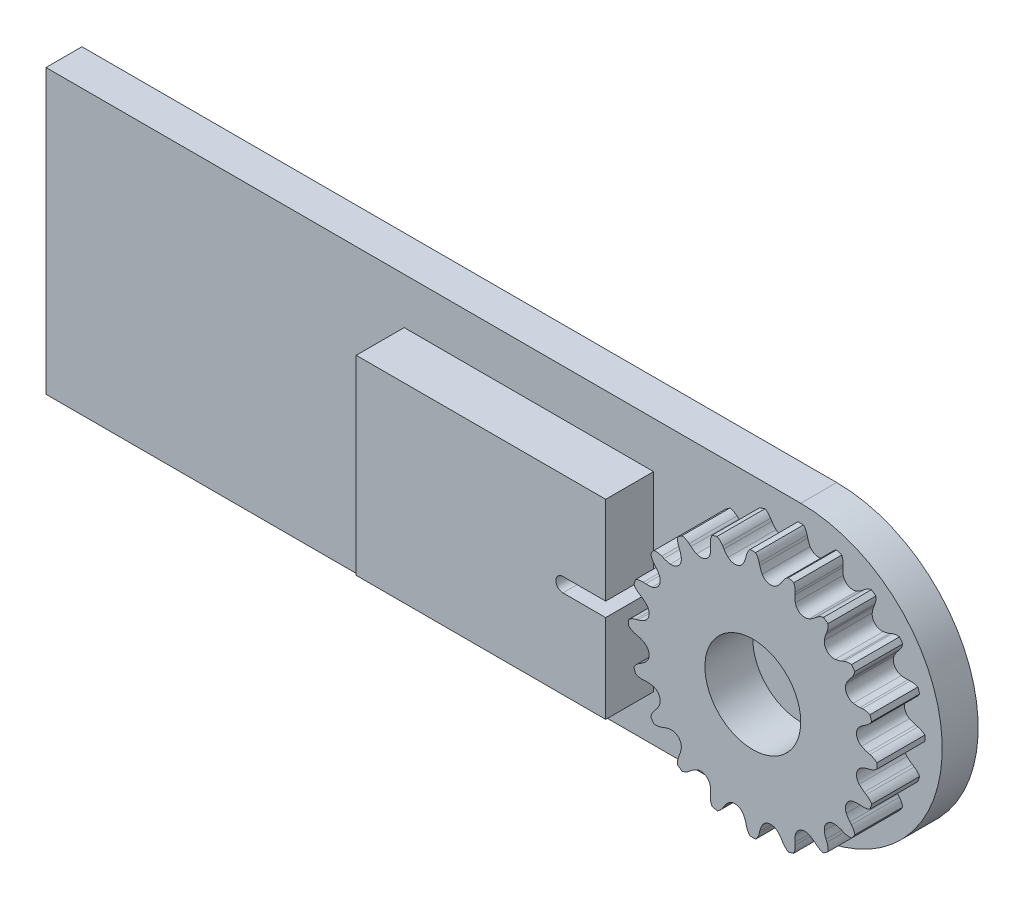
SolidWorks part; units mm, degrees
ref_plane "Front Plane" through (0, 0, 0) normal (0, 0, 1) x (1, 0, 0)
ref_plane "Top Plane" through (0, 0, 0) normal (0, 1, 0) x (1, 0, 0)
ref_plane "Right Plane" through (0, 0, 0) normal (1, 0, 0) x (0, 0, -1)
sketch "Sketch3" plane through (0, 0, 0) normal (1, 0, 0) x (0, 0, -1)
  line L5 (6.35, -43.7634) -> (-6.35, -43.7634)
  line L6 (6.35, -43.7634) -> (6.35, 43.7634)
  line L7 (6.35, 43.7634) -> (-6.35, 43.7634)
  line L8 (-6.35, -43.7634) -> (-6.35, 43.7634)
  line L9 (6.35, -43.7634) -> (-6.35, 43.7634) construction
  line L10 (6.35, 43.7634) -> (-6.35, -43.7634) construction
  line L11 (6.35, -37.5) -> (15.875, -37.5)
  line L12 (6.35, -37.5) -> (6.35, 37.5)
  line L13 (6.35, 37.5) -> (15.875, 37.5)
  line L14 (15.875, -37.5) -> (15.875, 37.5)
  line L15 (6.35, -37.5) -> (15.875, 37.5) construction
  line L16 (6.35, 37.5) -> (15.875, -37.5) construction
  point P0 (11.1125, 0)
  point P1 (0, 0)
  point P4 (0, 0)
  dimension "D1" = 9.525
  dimension "D2" = 12.7
  dimension "D3" = 75
extrude "Boss-Extrude3" add sketch "Sketch3" against normal blind 200 separate body contours L11 L14 L13 L6 region at (0, 0, -11.1125)
sketch "Sketch4" plane through (0, 0, -15.875) normal (0, 0, -1) x (-1, 0, 0)
  line L0 (200, 37.5) -> (0, 37.5) construction
  arc A0 (0, 37.5) -> (0, -37.5) centre (0, 0) ccw
  line M1 (0, 37.5) -> (0, -37.5)
extrude "Boss-Extrude4" add sketch "Sketch4" against normal up to surface (9.525 mm away) contours A0 M1 region at (15.9155, 0, -15.875) up to face at (-100, 0, -6.35)
sketch "Sketch1" plane through (0, 0, 0) normal (0, 0, 1) x (1, 0, 0)
  circle A0 centre (0, 0) radius 12.7
  circle A1 centre (0, 0) radius 9.525
  circle A2 centre (0, 0) radius 25
  circle A3 centre (0, 0) radius 30.319 construction
  dimension "D1" = 25.4
  dimension "D2" = 19.05
  dimension "D3" = 50
  dimension "D4" = 60.638
extrude "Boss-Extrude1" add sketch "Sketch1" against normal mid plane 12.7 separate body contours A2 A0 region at (-24.2929, 0, 0)
sketch "Sketch2" plane through (0, 0, 6.35) normal (0, 0, -1) x (-1, 0, 0)
  line L0 (-24.1305, -19.6378) -> (-23.5464, -19.3994)
  line L1 (-19.3994, -23.5464) -> (-19.6378, -24.1305)
  line L2 (-16.8811, -26.1334) -> (-16.3992, -25.7262)
  line L3 (-11.1737, -28.3887) -> (-11.2199, -29.0179)
  line L4 (-7.9792, -30.0709) -> (-7.6467, -29.5347)
  line L5 (-1.8543, -30.4521) -> (-1.7038, -31.0648)
  line L6 (1.7038, -31.0648) -> (1.8543, -30.4521)
  line L7 (7.6467, -29.5347) -> (7.9792, -30.0709)
  line L8 (11.2199, -29.0179) -> (11.1737, -28.3887)
  line L9 (16.3992, -25.7262) -> (16.8811, -26.1334)
  line L10 (19.6378, -24.1305) -> (19.3994, -23.5464)
  line L11 (23.5464, -19.3994) -> (24.1305, -19.6378)
  line L12 (26.1334, -16.8811) -> (25.7262, -16.3992)
  line L13 (28.3887, -11.1737) -> (29.0179, -11.2199)
  line L14 (30.0709, -7.9792) -> (29.5347, -7.6467)
  line L15 (30.4521, -1.8543) -> (31.0648, -1.7038)
  line L16 (31.0648, 1.7038) -> (30.4521, 1.8543)
  line L17 (29.5347, 7.6467) -> (30.0709, 7.9792)
  line L18 (29.0179, 11.2199) -> (28.3887, 11.1737)
  line L19 (25.7262, 16.3992) -> (26.1334, 16.8811)
  line L20 (24.1305, 19.6378) -> (23.5464, 19.3994)
  line L21 (19.3994, 23.5464) -> (19.6378, 24.1305)
  line L22 (16.8811, 26.1334) -> (16.3992, 25.7262)
  line L23 (11.1737, 28.3887) -> (11.2199, 29.0179)
  line L24 (7.9792, 30.0709) -> (7.6467, 29.5347)
  line L25 (1.8543, 30.4521) -> (1.7038, 31.0648)
  line L26 (-1.7038, 31.0648) -> (-1.8543, 30.4521)
  line L27 (-7.6467, 29.5347) -> (-7.9792, 30.0709)
  line L28 (-11.2199, 29.0179) -> (-11.1737, 28.3887)
  line L29 (-16.3992, 25.7262) -> (-16.8811, 26.1334)
  line L30 (-19.6378, 24.1305) -> (-19.3994, 23.5464)
  line L31 (-23.5464, 19.3994) -> (-24.1305, 19.6378)
  line L32 (-26.1334, 16.8811) -> (-25.7262, 16.3992)
  line L33 (-28.3887, 11.1737) -> (-29.0179, 11.2199)
  line L34 (-30.0709, 7.9792) -> (-29.5347, 7.6467)
  line L35 (-30.4521, 1.8543) -> (-31.0648, 1.7038)
  line L36 (-31.0648, -1.7038) -> (-30.4521, -1.8543)
  line L37 (-29.5347, -7.6467) -> (-30.0709, -7.9792)
  line L38 (-29.0179, -11.2199) -> (-28.3887, -11.1737)
  line L39 (-25.7262, -16.3992) -> (-26.1334, -16.8811)
  arc A0 (-27.0344, -18.7375) -> (-26.1745, -19.921) centre (0, 0) ccw
  arc A1 (-26.1745, -19.921) -> (-24.1305, -19.6378) centre (-25.7075, -15.7735) ccw
  arc A2 (-21.8429, -18.9557) -> (-23.5464, -19.3994) centre (-21.0319, -25.5609) ccw
  arc A3 (-18.9557, -21.8429) -> (-21.8429, -18.9557) centre (-21.5272, -21.5272) ccw
  arc A4 (-19.3994, -23.5464) -> (-18.9557, -21.8429) centre (-25.5609, -21.0319) ccw
  arc A5 (-19.6378, -24.1305) -> (-19.921, -26.1745) centre (-15.7735, -25.7075) ccw
  arc A6 (-19.921, -26.1745) -> (-18.7375, -27.0344) centre (0, 0) ccw
  arc A7 (-18.7375, -27.0344) -> (-16.8811, -26.1334) centre (-19.575, -22.9455) ccw
  arc A8 (-14.9162, -24.7778) -> (-16.3992, -25.7262) centre (-12.1038, -30.8091) ccw
  arc A9 (-11.2781, -26.6315) -> (-14.9162, -24.7778) centre (-13.8213, -27.1259) ccw
  arc A10 (-11.1737, -28.3887) -> (-11.2781, -26.6315) centre (-17.8106, -27.9013) ccw
  arc A11 (-11.2199, -29.0179) -> (-10.8576, -31.0493) centre (-7.0574, -29.3236) ccw
  arc A12 (-10.8576, -31.0493) -> (-9.4663, -31.5014) centre (0, 0) ccw
  arc A13 (-9.4663, -31.5014) -> (-7.9792, -30.0709) centre (-11.5264, -27.8715) ccw
  arc A14 (-6.5294, -28.1745) -> (-7.6467, -29.5347) centre (-1.9909, -33.0415) ccw
  arc A15 (-2.4965, -28.8132) -> (-6.5294, -28.1745) centre (-4.7625, -30.0692) ccw
  arc A16 (-1.8543, -30.4521) -> (-2.4965, -28.8132) centre (-8.317, -32.0395) ccw
  arc A17 (-1.7038, -31.0648) -> (-0.7315, -32.8849) centre (2.3495, -30.0692) ccw
  arc A18 (-0.7315, -32.8849) -> (0.7315, -32.8849) centre (0, 0) ccw
  arc A19 (0.7315, -32.8849) -> (1.7038, -31.0648) centre (-2.3495, -30.0692) ccw
  arc A20 (2.4965, -28.8132) -> (1.8543, -30.4521) centre (8.317, -32.0395) ccw
  arc A21 (6.5294, -28.1745) -> (2.4965, -28.8132) centre (4.7625, -30.0692) ccw
  arc A22 (7.6467, -29.5347) -> (6.5294, -28.1745) centre (1.9909, -33.0415) ccw
  arc A23 (7.9792, -30.0709) -> (9.4663, -31.5014) centre (11.5264, -27.8715) ccw
  arc A24 (9.4663, -31.5014) -> (10.8576, -31.0493) centre (0, 0) ccw
  arc A25 (10.8576, -31.0493) -> (11.2199, -29.0179) centre (7.0574, -29.3236) ccw
  arc A26 (11.2781, -26.6315) -> (11.1737, -28.3887) centre (17.8106, -27.9013) ccw
  arc A27 (14.9162, -24.7778) -> (11.2781, -26.6315) centre (13.8213, -27.1259) ccw
  arc A28 (16.3992, -25.7262) -> (14.9162, -24.7778) centre (12.1038, -30.8091) ccw
  arc A29 (16.8811, -26.1334) -> (18.7375, -27.0344) centre (19.575, -22.9455) ccw
  arc A30 (18.7375, -27.0344) -> (19.921, -26.1745) centre (0, 0) ccw
  arc A31 (19.921, -26.1745) -> (19.6378, -24.1305) centre (15.7735, -25.7075) ccw
  arc A32 (18.9557, -21.8429) -> (19.3994, -23.5464) centre (25.5609, -21.0319) ccw
  arc A33 (21.8429, -18.9557) -> (18.9557, -21.8429) centre (21.5272, -21.5272) ccw
  arc A34 (23.5464, -19.3994) -> (21.8429, -18.9557) centre (21.0319, -25.5609) ccw
  arc A35 (24.1305, -19.6378) -> (26.1745, -19.921) centre (25.7075, -15.7735) ccw
  arc A36 (26.1745, -19.921) -> (27.0344, -18.7375) centre (0, 0) ccw
  arc A37 (27.0344, -18.7375) -> (26.1334, -16.8811) centre (22.9455, -19.575) ccw
  arc A38 (24.7778, -14.9162) -> (25.7262, -16.3992) centre (30.8091, -12.1038) ccw
  arc A39 (26.6315, -11.2781) -> (24.7778, -14.9162) centre (27.1259, -13.8213) ccw
  arc A40 (28.3887, -11.1737) -> (26.6315, -11.2781) centre (27.9013, -17.8106) ccw
  arc A41 (29.0179, -11.2199) -> (31.0493, -10.8576) centre (29.3236, -7.0574) ccw
  arc A42 (31.0493, -10.8576) -> (31.5014, -9.4663) centre (0, 0) ccw
  arc A43 (31.5014, -9.4663) -> (30.0709, -7.9792) centre (27.8715, -11.5264) ccw
  arc A44 (28.1745, -6.5294) -> (29.5347, -7.6467) centre (33.0415, -1.9909) ccw
  arc A45 (28.8132, -2.4965) -> (28.1745, -6.5294) centre (30.0692, -4.7625) ccw
  arc A46 (30.4521, -1.8543) -> (28.8132, -2.4965) centre (32.0395, -8.317) ccw
  arc A47 (31.0648, -1.7038) -> (32.8849, -0.7315) centre (30.0692, 2.3495) ccw
  arc A48 (32.8849, -0.7315) -> (32.8849, 0.7315) centre (0, 0) ccw
  arc A49 (32.8849, 0.7315) -> (31.0648, 1.7038) centre (30.0692, -2.3495) ccw
  arc A50 (28.8132, 2.4965) -> (30.4521, 1.8543) centre (32.0395, 8.317) ccw
  arc A51 (28.1745, 6.5294) -> (28.8132, 2.4965) centre (30.0692, 4.7625) ccw
  arc A52 (29.5347, 7.6467) -> (28.1745, 6.5294) centre (33.0415, 1.9909) ccw
  arc A53 (30.0709, 7.9792) -> (31.5014, 9.4663) centre (27.8715, 11.5264) ccw
  arc A54 (31.5014, 9.4663) -> (31.0493, 10.8576) centre (0, 0) ccw
  arc A55 (31.0493, 10.8576) -> (29.0179, 11.2199) centre (29.3236, 7.0574) ccw
  arc A56 (26.6315, 11.2781) -> (28.3887, 11.1737) centre (27.9013, 17.8106) ccw
  arc A57 (24.7778, 14.9162) -> (26.6315, 11.2781) centre (27.1259, 13.8213) ccw
  arc A58 (25.7262, 16.3992) -> (24.7778, 14.9162) centre (30.8091, 12.1038) ccw
  arc A59 (26.1334, 16.8811) -> (27.0344, 18.7375) centre (22.9455, 19.575) ccw
  arc A60 (27.0344, 18.7375) -> (26.1745, 19.921) centre (0, 0) ccw
  arc A61 (26.1745, 19.921) -> (24.1305, 19.6378) centre (25.7075, 15.7735) ccw
  arc A62 (21.8429, 18.9557) -> (23.5464, 19.3994) centre (21.0319, 25.5609) ccw
  arc A63 (18.9557, 21.8429) -> (21.8429, 18.9557) centre (21.5272, 21.5272) ccw
  arc A64 (19.3994, 23.5464) -> (18.9557, 21.8429) centre (25.5609, 21.0319) ccw
  arc A65 (19.6378, 24.1305) -> (19.921, 26.1745) centre (15.7735, 25.7075) ccw
  arc A66 (19.921, 26.1745) -> (18.7375, 27.0344) centre (0, 0) ccw
  arc A67 (18.7375, 27.0344) -> (16.8811, 26.1334) centre (19.575, 22.9455) ccw
  arc A68 (14.9162, 24.7778) -> (16.3992, 25.7262) centre (12.1038, 30.8091) ccw
  arc A69 (11.2781, 26.6315) -> (14.9162, 24.7778) centre (13.8213, 27.1259) ccw
  arc A70 (11.1737, 28.3887) -> (11.2781, 26.6315) centre (17.8106, 27.9013) ccw
  arc A71 (11.2199, 29.0179) -> (10.8576, 31.0493) centre (7.0574, 29.3236) ccw
  arc A72 (10.8576, 31.0493) -> (9.4663, 31.5014) centre (0, 0) ccw
  arc A73 (9.4663, 31.5014) -> (7.9792, 30.0709) centre (11.5264, 27.8715) ccw
  arc A74 (6.5294, 28.1745) -> (7.6467, 29.5347) centre (1.9909, 33.0415) ccw
  arc A75 (2.4965, 28.8132) -> (6.5294, 28.1745) centre (4.7625, 30.0692) ccw
  arc A76 (1.8543, 30.4521) -> (2.4965, 28.8132) centre (8.317, 32.0395) ccw
  arc A77 (1.7038, 31.0648) -> (0.7315, 32.8849) centre (-2.3495, 30.0692) ccw
  arc A78 (0.7315, 32.8849) -> (-0.7315, 32.8849) centre (0, 0) ccw
  arc A79 (-0.7315, 32.8849) -> (-1.7038, 31.0648) centre (2.3495, 30.0692) ccw
  arc A80 (-2.4965, 28.8132) -> (-1.8543, 30.4521) centre (-8.317, 32.0395) ccw
  arc A81 (-6.5294, 28.1745) -> (-2.4965, 28.8132) centre (-4.7625, 30.0692) ccw
  arc A82 (-7.6467, 29.5347) -> (-6.5294, 28.1745) centre (-1.9909, 33.0415) ccw
  arc A83 (-7.9792, 30.0709) -> (-9.4663, 31.5014) centre (-11.5264, 27.8715) ccw
  arc A84 (-9.4663, 31.5014) -> (-10.8576, 31.0493) centre (0, 0) ccw
  arc A85 (-10.8576, 31.0493) -> (-11.2199, 29.0179) centre (-7.0574, 29.3236) ccw
  arc A86 (-11.2781, 26.6315) -> (-11.1737, 28.3887) centre (-17.8106, 27.9013) ccw
  arc A87 (-14.9162, 24.7778) -> (-11.2781, 26.6315) centre (-13.8213, 27.1259) ccw
  arc A88 (-16.3992, 25.7262) -> (-14.9162, 24.7778) centre (-12.1038, 30.8091) ccw
  arc A89 (-16.8811, 26.1334) -> (-18.7375, 27.0344) centre (-19.575, 22.9455) ccw
  arc A90 (-18.7375, 27.0344) -> (-19.921, 26.1745) centre (0, 0) ccw
  arc A91 (-19.921, 26.1745) -> (-19.6378, 24.1305) centre (-15.7735, 25.7075) ccw
  arc A92 (-18.9557, 21.8429) -> (-19.3994, 23.5464) centre (-25.5609, 21.0319) ccw
  arc A93 (-21.8429, 18.9557) -> (-18.9557, 21.8429) centre (-21.5272, 21.5272) ccw
  arc A94 (-23.5464, 19.3994) -> (-21.8429, 18.9557) centre (-21.0319, 25.5609) ccw
  arc A95 (-24.1305, 19.6378) -> (-26.1745, 19.921) centre (-25.7075, 15.7735) ccw
  arc A96 (-26.1745, 19.921) -> (-27.0344, 18.7375) centre (0, 0) ccw
  arc A97 (-27.0344, 18.7375) -> (-26.1334, 16.8811) centre (-22.9455, 19.575) ccw
  arc A98 (-24.7778, 14.9162) -> (-25.7262, 16.3992) centre (-30.8091, 12.1038) ccw
  arc A99 (-26.6315, 11.2781) -> (-24.7778, 14.9162) centre (-27.1259, 13.8213) ccw
  arc A100 (-28.3887, 11.1737) -> (-26.6315, 11.2781) centre (-27.9013, 17.8106) ccw
  arc A101 (-29.0179, 11.2199) -> (-31.0493, 10.8576) centre (-29.3236, 7.0574) ccw
  arc A102 (-31.0493, 10.8576) -> (-31.5014, 9.4663) centre (0, 0) ccw
  arc A103 (-31.5014, 9.4663) -> (-30.0709, 7.9792) centre (-27.8715, 11.5264) ccw
  arc A104 (-28.1745, 6.5294) -> (-29.5347, 7.6467) centre (-33.0415, 1.9909) ccw
  arc A105 (-28.8132, 2.4965) -> (-28.1745, 6.5294) centre (-30.0692, 4.7625) ccw
  arc A106 (-30.4521, 1.8543) -> (-28.8132, 2.4965) centre (-32.0395, 8.317) ccw
  arc A107 (-31.0648, 1.7038) -> (-32.8849, 0.7315) centre (-30.0692, -2.3495) ccw
  arc A108 (-32.8849, 0.7315) -> (-32.8849, -0.7315) centre (0, 0) ccw
  arc A109 (-32.8849, -0.7315) -> (-31.0648, -1.7038) centre (-30.0692, 2.3495) ccw
  arc A110 (-28.8132, -2.4965) -> (-30.4521, -1.8543) centre (-32.0395, -8.317) ccw
  arc A111 (-28.1745, -6.5294) -> (-28.8132, -2.4965) centre (-30.0692, -4.7625) ccw
  arc A112 (-29.5347, -7.6467) -> (-28.1745, -6.5294) centre (-33.0415, -1.9909) ccw
  arc A113 (-30.0709, -7.9792) -> (-31.5014, -9.4663) centre (-27.8715, -11.5264) ccw
  arc A114 (-31.5014, -9.4663) -> (-31.0493, -10.8576) centre (0, 0) ccw
  arc A115 (-31.0493, -10.8576) -> (-29.0179, -11.2199) centre (-29.3236, -7.0574) ccw
  arc A116 (-26.6315, -11.2781) -> (-28.3887, -11.1737) centre (-27.9013, -17.8106) ccw
  arc A117 (-24.7778, -14.9162) -> (-26.6315, -11.2781) centre (-27.1259, -13.8213) ccw
  arc A118 (-25.7262, -16.3992) -> (-24.7778, -14.9162) centre (-30.8091, -12.1038) ccw
  arc A119 (-26.1334, -16.8811) -> (-27.0344, -18.7375) centre (-22.9455, -19.575) ccw
  circle A121 centre (0, 0) radius 25
  point P280 (0, 0)
extrude "Boss-Extrude2" add sketch "Sketch2" along normal up to surface (12.7 mm away) up to face at (12.7, 0, -6.35)
sketch "Sketch5" plane through (0, 0, -6.35) normal (0, 0, 1) x (1, 0, 0)
  line L0 (-30.319, 0) -> (-50.319, 0) construction
  line L3 (-30.319, -1.8859) -> (-50.319, -1.8859)
  line L4 (-30.319, 1.8859) -> (-50.319, 1.8859)
  arc A2 (-30.319, -1.8859) -> (-30.319, 1.8859) centre (-30.319, 0) ccw
  arc A3 (-50.319, 1.8859) -> (-50.319, -1.8859) centre (-50.319, 0) ccw
  circle A4 centre (0, 0) radius 30.319 construction
  point P3 (-40.319, 0)
  point P9 (-32.8849, -0.7315)
  point P10 (-30.319, 0)
  dimension "D1" = 3.7719
  dimension "D2" = 20
extrude "Cut-Extrude1" cut sketch "Sketch5" against normal up to surface (9.525 mm away) contours L4 A3 L3 A2 region at (-40.319, 0, -6.35) up to face at (-90.625, 0, -15.875)
sketch "Sketch6" plane through (0, 0, 0) normal (0, 0, 1) x (1, 0, 0)
  line L1 (-105.0941, -25.2606) -> (-38.9916, -25.2606)
  line L2 (-105.0941, -25.2606) -> (-105.0941, 25.2606)
  line L3 (-105.0941, 25.2606) -> (-38.9916, 25.2606)
  line L4 (-38.9916, -25.2606) -> (-38.9916, 25.2606)
  line L5 (-105.0941, -25.2606) -> (-38.9916, 25.2606) construction
  line L6 (-105.0941, 25.2606) -> (-38.9916, -25.2606) construction
  point P0 (-72.0429, 0)
extrude "Boss-Extrude5" add sketch "Sketch6" along normal mid plane 12.7 separate body
sketch "Sketch8" plane through (0, 0, 6.35) normal (0, 0, 1) x (1, 0, 0)
  line L2 (-50.319, -1.8859) -> (-30.319, -1.8859)
  line L3 (-30.319, 1.8859) -> (-50.319, 1.8859)
  line L4 (-50.319, -1.8859) -> (-30.319, -1.8859)
  line L5 (-30.319, 1.8859) -> (-50.319, 1.8859)
  arc A2 (-50.319, 1.8859) -> (-50.319, -1.8859) centre (-50.319, 0) ccw
  arc A3 (-30.319, -1.8859) -> (-30.319, 1.8859) centre (-30.319, 0) ccw
  arc A4 (-50.319, 1.8859) -> (-50.319, -1.8859) centre (-50.319, 0) ccw
  arc A5 (-30.319, -1.8859) -> (-30.319, 1.8859) centre (-30.319, 0) ccw
  dimension "D1" = 0
extrude "Cut-Extrude2" cut sketch "Sketch8" against normal blind 12.7
